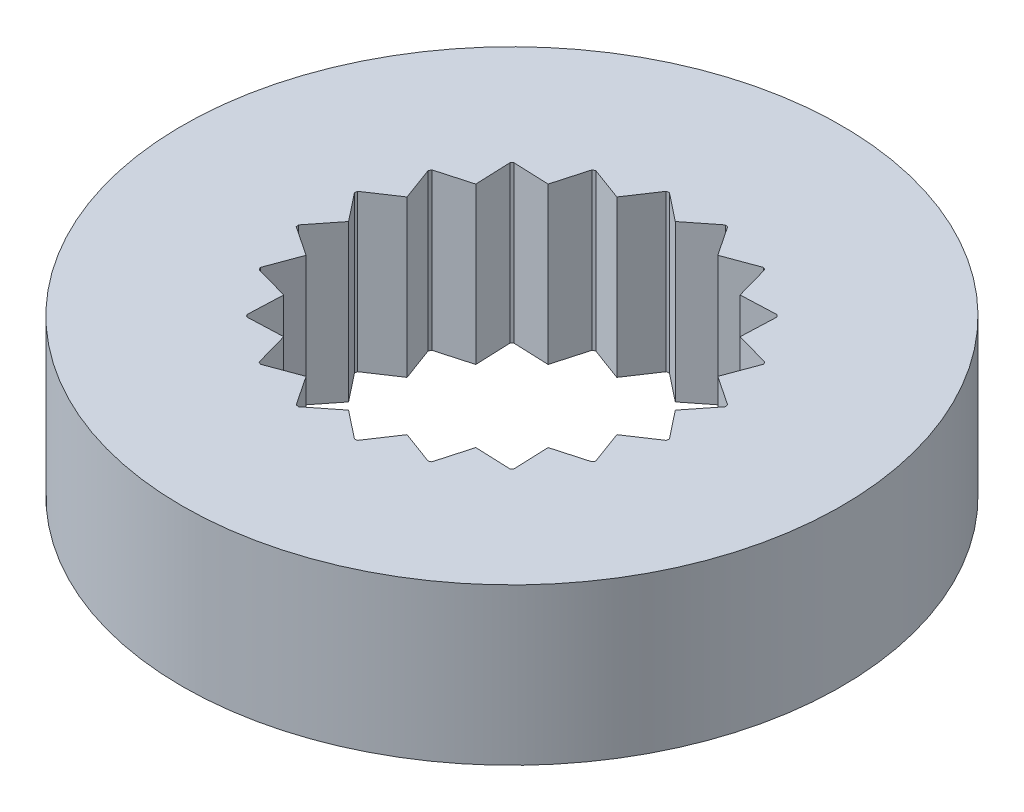
SolidWorks part; units mm, degrees
ref_plane "Front Plane" through (0, 0, 0) normal (0, 0, 1) x (1, 0, 0)
ref_plane "Top Plane" through (0, 0, 0) normal (0, 1, 0) x (1, 0, 0)
ref_plane "Right Plane" through (0, 0, 0) normal (1, 0, 0) x (0, 0, -1)
sketch "Sketch1" plane through (0, 0, 0) normal (0, 1, 0) x (1, 0, 0)
  circle A0 centre (0, 0) radius 2.6
  dimension "D1" = 5.2
sketch "Sketch2" plane through (0, 0, 0) normal (0, 1, 0) x (1, 0, 0)
  line L0 (-0.38, 2.6) -> (0, 2.3)
  line L1 (0, 2.3) -> (0.38, 2.6)
  line L2 (0.38, 2.6) -> (-0.38, 2.6)
  circle A0 centre (0, 0) radius 2.6 construction
  point P3 (0, 2.6)
  dimension "D1" = 0.3
  dimension "D2" = 0.76
sketch "Sketch3" plane through (0, 0, 0) normal (0, 1, 0) x (1, 0, 0)
  circle A1 centre (0, 0) radius 4.64
  circle A2 centre (0, 0) radius 2.64
  circle A3 centre (0, 0) radius 2.64
  dimension "D2" = 2
  dimension "D1" = 0.04
extrude "Boss-Extrude2" add sketch "Sketch3" along normal blind 2.2
sketch "Sketch4" plane through (0, 0, 0) normal (0, 1, 0) x (1, 0, 0)
  line L0 (0, 2.3) -> (-0.8528, 2.9733)
  line L1 (-0.8528, 2.9733) -> (0.8528, 2.9733)
  line L2 (0.8528, 2.9733) -> (0, 2.3)
  line L3 (0, 2.3) -> (0.38, 2.6) construction
  line L4 (-0.38, 2.6) -> (0, 2.3) construction
extrude "Boss-Extrude3" add sketch "Sketch4" along normal blind 2.2
pattern_circular "CirPattern2" count 20 over 360 about axis through (0, 2.2, 0) along (0, 1, 0) of "Boss-Extrude3"
